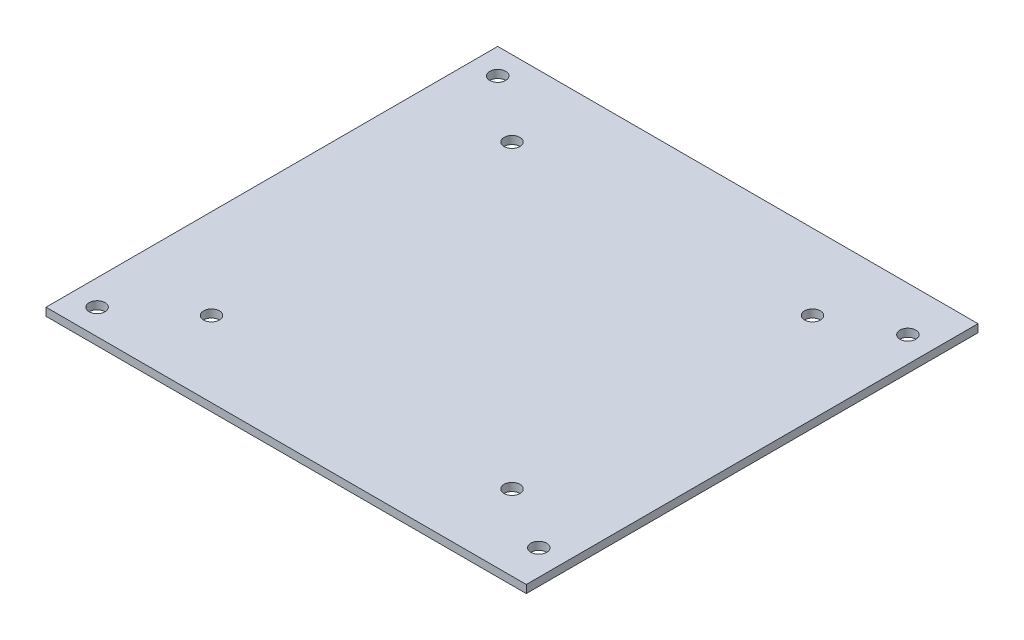
SolidWorks part; units mm, degrees
ref_plane "Front Plane" through (0, 0, 0) normal (0, 0, 1) x (1, 0, 0)
ref_plane "Top Plane" through (0, 0, 0) normal (0, 1, 0) x (1, 0, 0)
ref_plane "Right Plane" through (0, 0, 0) normal (1, 0, 0) x (0, 0, -1)
sketch "Sketch2" plane through (0, 0, 0) normal (0, 1, 0) x (1, 0, 0)
  line L1 (-47.95, -45.1) -> (47.95, -45.1)
  line L2 (-47.95, -45.1) -> (-47.95, 45.1)
  line L3 (-47.95, 45.1) -> (47.95, 45.1)
  line L4 (47.95, -45.1) -> (47.95, 45.1)
  line L5 (-47.95, -45.1) -> (47.95, 45.1) construction
  line L6 (-47.95, 45.1) -> (47.95, -45.1) construction
  circle A0 centre (30, 30) radius 1.5875
  circle A1 centre (30, -30) radius 1.5875
  circle A2 centre (-30, -30) radius 1.5875
  circle A3 centre (-30, 30) radius 1.5875
  circle A4 centre (-42.85, 40) radius 1.5875
  circle A5 centre (-42.85, -40) radius 1.5875
  circle A6 centre (42.85, 36.2) radius 1.5875
  circle A7 centre (42.85, -37.5) radius 1.5875
  point P0 (0, 0)
  point P6 (30, 30)
  point P9 (42.85, 36.2)
  point P10 (42.85, -37.5)
  point P11 (-42.85, 40)
  point P18 (0, 0)
  point P19 (-42.85, -40)
  dimension "D1" = 4
extrude "Boss-Extrude1" add sketch "Sketch2" along normal blind 1.58 contours A2 | A5 | A3 | A6 | A0 | A1 | A7 | A4 | L2 L1 L4 L3 region at (30, 0, -30) region at (30, 0, 30) region at (-30, 0, 30) region at (-30, 0, -30) region at (-42.85, 0, -40) region at (-42.85, 0, 40) region at (42.85, 0, -36.2) region at (42.85, 0, 37.5)
